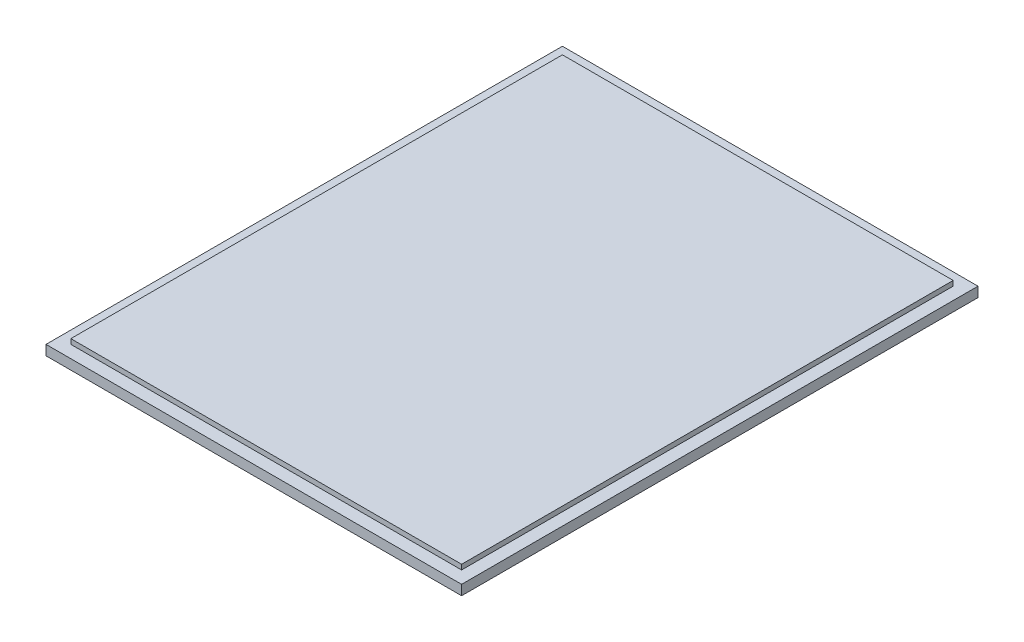
SolidWorks part; units mm, degrees
ref_plane "Front Plane" through (0, 0, 0) normal (0, 0, 1) x (1, 0, 0)
ref_plane "Top Plane" through (0, 0, 0) normal (0, 1, 0) x (1, 0, 0)
ref_plane "Right Plane" through (0, 0, 0) normal (1, 0, 0) x (0, 0, -1)
sketch "Sketch1" plane through (0, 0, 0) normal (0, 1, 0) x (1, 0, 0)
  line L0 (-27.3295, -53.5187) -> (-27.3295, 45.4813)
  line L1 (53.8705, -56.0187) -> (-29.8295, -56.0187)
  line L2 (53.8705, -56.0187) -> (53.8705, 47.9813)
  line L3 (53.8705, 47.9813) -> (-29.8295, 47.9813)
  line L4 (-29.8295, -56.0187) -> (-29.8295, 47.9813)
  line L5 (51.3705, 45.4813) -> (-27.3295, 45.4813)
  line L6 (51.3705, -53.5187) -> (51.3705, 45.4813)
  line L7 (51.3705, -53.5187) -> (-27.3295, -53.5187)
  point P0 (0, 0)
  dimension "D1" = 83.7
  dimension "D2" = 104
  dimension "D4" = 99
  dimension "D5" = 78.7
  dimension "D3" = 2.5
extrude "Boss-Extrude2" add sketch "Sketch1" along normal blind 3 contours L7 L6 L5 L0 | L0 L5 L6 L7 region at (12.0205, 0, 4.0187)
extrude "Boss-Extrude3" add sketch "Sketch1<5>" along normal blind 2
sketch "Sketch1<5>" plane through (0, 0, 0) normal (0, 1, 0) x (1, 0, 0) same geometry as "Sketch1"
